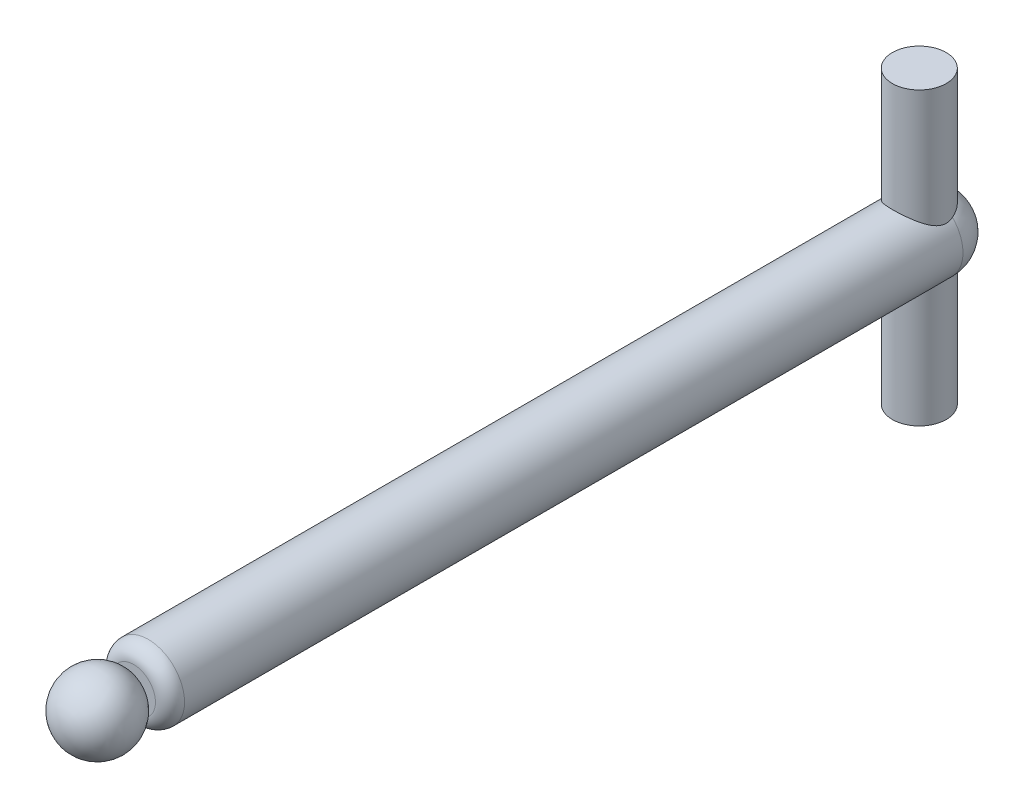
SolidWorks part; units mm, degrees
ref_plane "Front Plane" through (0, 0, 0) normal (0, 0, 1) x (1, 0, 0)
ref_plane "Top Plane" through (0, 0, 0) normal (0, 1, 0) x (1, 0, 0)
ref_plane "Right Plane" through (0, 0, 0) normal (1, 0, 0) x (0, 0, -1)
sketch "Sketch1" plane through (0, 0, 0) normal (0, 0, 1) x (1, 0, 0)
  circle A0 centre (0, 0) radius 2.5
  dimension "D1" = 5
extrude "Boss-Extrude1" add sketch "Sketch1" along normal blind 57
sketch "Sketch2" plane through (0, 0, 0) normal (0, 1, 0) x (1, 0, 0)
  line L0 (-2.5, -57) -> (2.5, -57)
sketch "Sketch3" plane through (0, 0, 0) normal (0, 1, 0) x (1, 0, 0)
  line L0 (-2.5, -57) -> (2.5, -57) construction
  line L1 (0, -57) -> (0, -62)
  line L3 (0, -29.8406) -> (-1.5, -29.8406)
  line L4 (0, -29.8406) -> (0, -27.9123)
  line L5 (0, -27.9123) -> (-1.5, -27.9123)
  line L6 (-1.5, -29.8406) -> (-1.5, -27.9123)
  arc A1 (0, -57) -> (0, -62) centre (0, -59.5) ccw
  dimension "D1" = 1.5
  dimension "D2" = 2.5
revolve "Revolve1" add sketch "Sketch3" angle 360 about L1
fillet "Fillet1" radius 1 1 edges at (2.5, 0, 57)
sketch "Sketch4" plane through (0, 0, 0) normal (0, 1, 0) x (1, 0, 0)
  circle A0 centre (0, -3) radius 1.85
  dimension "D1" = 3.7
  dimension "D2" = 3
extrude "Boss-Extrude2" add sketch "Sketch4" along normal blind 10 and the other way blind 10 contours A0
fillet "Fillet2" radius 2.5 1 edges at (2.5, 0, 0)
